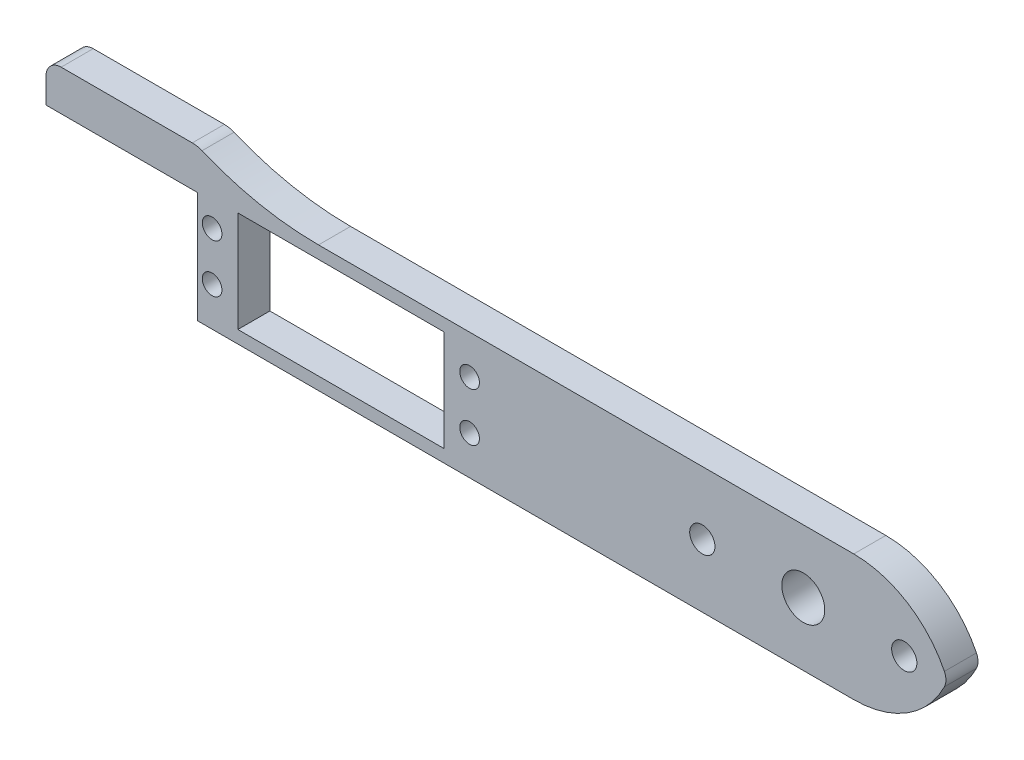
SolidWorks part; units mm, degrees
ref_plane "Front" through (0, 0, 0) normal (0, 0, 1) x (1, 0, 0)
ref_plane "Top" through (0, 0, 0) normal (0, 1, 0) x (1, 0, 0)
ref_plane "Right" through (0, 0, 0) normal (1, 0, 0) x (0, 0, -1)
sketch "Sketch1" plane through (0, 0, 0) normal (0, 0, 1) x (1, 0, 0)
  line L0 (-75, 0) -> (75, 0) construction
  line L1 (75, 12.5) -> (-75, 12.5)
  line L2 (75, 12.5) -> (75, -12.5)
  line L3 (75, -12.5) -> (-75, -12.5)
  line L4 (-75, 12.5) -> (-75, -12.5)
  line L5 (75, 12.5) -> (-75, -12.5) construction
  line L6 (75, -12.5) -> (-75, 12.5) construction
  circle A0 centre (65, 0) radius 2.5
  circle A1 centre (25, 0) radius 2.5
  circle A2 centre (45, 0) radius 4.25
  point P0 (0, 0)
  dimension "D3" = 5
  dimension "D5" = 10
  dimension "D6" = 20
  dimension "D7" = 8.5
  dimension "D1" = 25
  dimension "D2" = 150
  dimension "D4" = 40
extrude "Boss-Extrude1" add sketch "Sketch1" along normal blind 6.35
fillet "Fillet1" radius 20 2 edges at (75, 12.5, 3.175) (75, -12.5, 3.175)
sketch "Sketch2" plane through (0, 0, 6.35) normal (0, 0, 1) x (1, 0, 0)
  line L0 (0, 0) -> (-75, 0) construction
  line L1 (-75, 12.5) -> (-75, -12.5) construction
  line L2 (-46.6, 12.5) -> (-46.6, -12.5) construction
  line L3 (-67, 10) -> (-26.2, 10)
  line L4 (-67, 10) -> (-67, -10)
  line L5 (-67, -10) -> (-26.2, -10)
  line L6 (-26.2, 10) -> (-26.2, -10)
  line L7 (-67, 10) -> (-26.2, -10) construction
  line L8 (-67, -10) -> (-26.2, 10) construction
  line L9 (55, 12.5) -> (-75, 12.5) construction
  line L10 (-75, -12.5) -> (55, -12.5) construction
  circle A0 centre (-72.1, 4.8) radius 1.95
  circle A1 centre (-72.1, -4.8) radius 1.95
  circle A2 centre (-21.1, 4.8) radius 1.95
  circle A3 centre (-21.1, -4.8) radius 1.95
  point P5 (-46.6, 0)
  dimension "D5" = 3.9
  dimension "D6" = 4.8
  dimension "D1" = 20
  dimension "D2" = 40.8
  dimension "D3" = 8
  dimension "D4" = 5.1
extrude "Cut-Extrude1" cut sketch "Sketch2" against normal up to surface (6.35 mm away) up to face at (27.5, 0, 0)
sketch "Sketch3" plane through (-75, 0, 0) normal (-1, 0, 0) x (0, 0, 1)
  line L0 (0, 12.5) -> (0, -12.5) construction
  line L1 (0, 9.5) -> (6.35, 9.5)
  line L2 (0, 9.5) -> (0, 17.5)
  line L3 (0, 17.5) -> (6.35, 17.5)
  line L4 (6.35, 9.5) -> (6.35, 17.5)
  line L5 (6.35, 12.5) -> (6.35, -12.5) construction
  line L6 (6.35, 12.5) -> (0, 12.5) construction
  dimension "D1" = 3
  dimension "D2" = 5
extrude "Boss-Extrude2" add sketch "Sketch3" along normal blind 30
fillet "Fillet2" radius 60 1 edges
fillet "Fillet4" radius 5 1 edges at (-75, 17.5, 3.175)
fillet "Fillet5" radius 3 2 edges at (73.5405, 0, 3.175) (-105, 17.5, 3.175)
